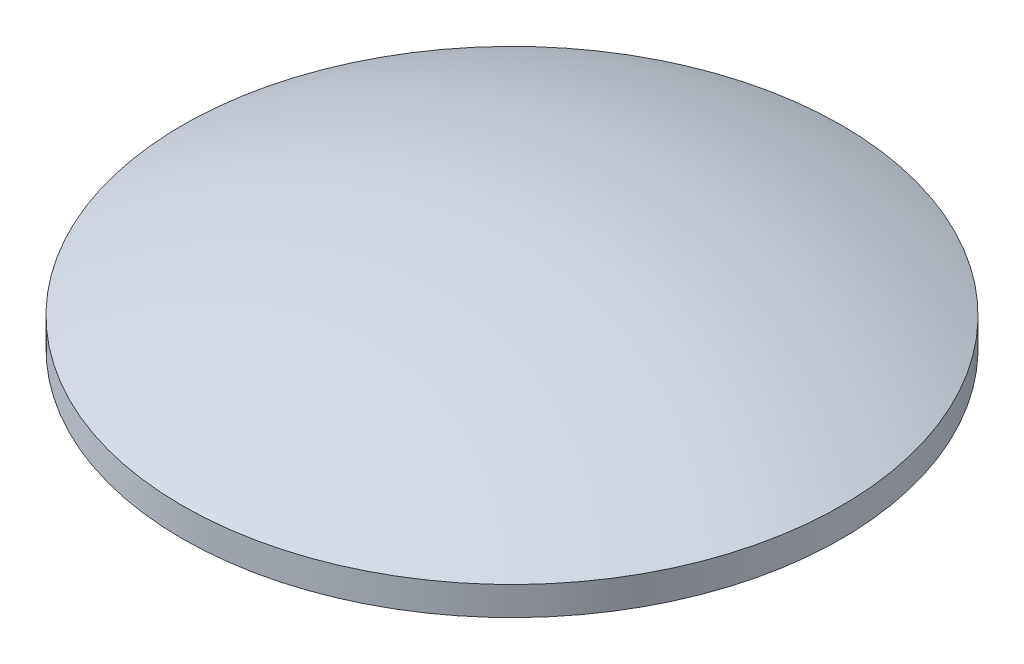
SolidWorks part; units mm, degrees
material "Plain Carbon Steel"
ref_plane "Front Plane" through (0, 0, 0) normal (0, 0, 1) x (1, 0, 0)
ref_plane "Top Plane" through (0, 0, 0) normal (0, 1, 0) x (1, 0, 0)
ref_plane "Right Plane" through (0, 0, 0) normal (1, 0, 0) x (0, 0, -1)
other "Configuration Table"
sketch "Sketch1" plane through (0, 0, 0) normal (0, 1, 0) x (1, 0, 0)
  circle A0 centre (0, 0) radius 2.921
  dimension "D1" = 5.842
extrude "Extrude1" add sketch "Sketch1" along normal blind 0.254
dome "Dome1" faces to dome 1 distance 0.635 reverse direction no elliptical dome no face at (0, 0.254, 2.921) parameters "D1"=0.635
